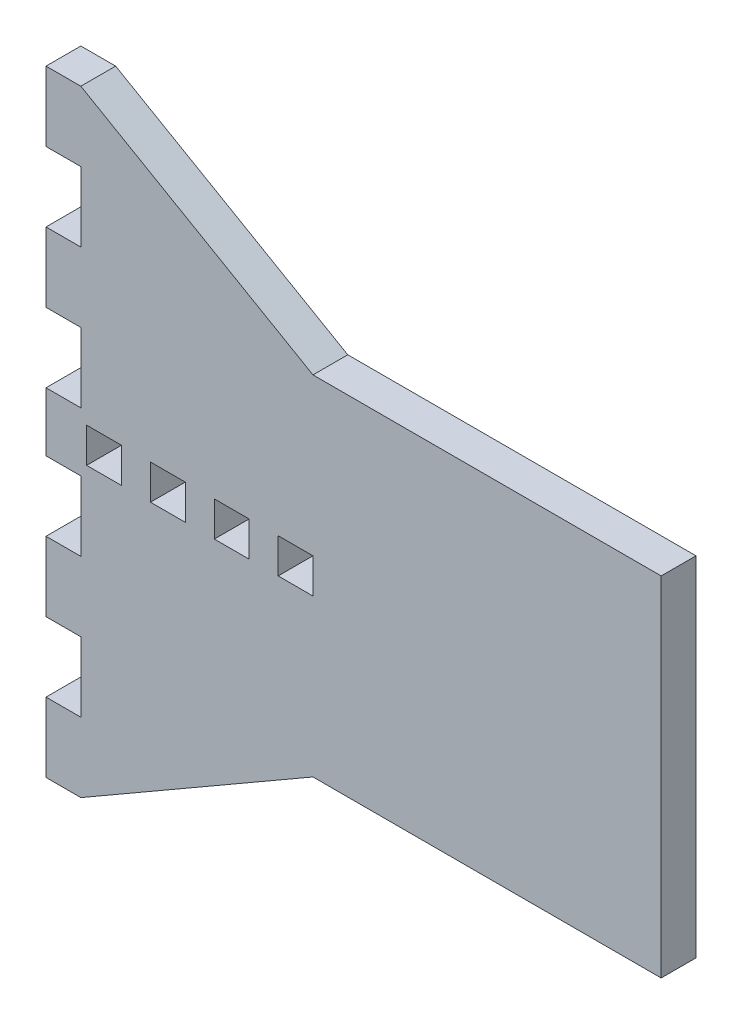
SolidWorks part; units mm, degrees
ref_plane "Front Plane" through (0, 0, 0) normal (0, 0, 1) x (1, 0, 0)
ref_plane "Top Plane" through (0, 0, 0) normal (0, 1, 0) x (1, 0, 0)
ref_plane "Right Plane" through (0, 0, 0) normal (1, 0, 0) x (0, 0, -1)
sketch "Sketch1" plane through (0, 0, 0) normal (0, 0, 1) x (1, 0, 0)
  line L0 (-66.7906, 0) -> (77.661, 0) construction
  line L1 (0, 53.9016) -> (0, -59.5601) construction
  line L9 (-35, 26.54) -> (-35, -26.54)
  line L10 (-15, 15) -> (15, 15)
  line L12 (-15, -15) -> (15, -15)
  line L13 (15, 15) -> (15, -15)
  line L14 (-15, 15) -> (15, -15) construction
  line L15 (-15, -15) -> (15, 15) construction
  line L16 (-35, 26.54) -> (-15, 15)
  line L17 (-15, -15) -> (-35, -26.54)
  circle A1 centre (0, 0) radius 11
  dimension "D1" = 22
  dimension "D2" = 30
  dimension "D3" = 30
  dimension "D4" = 35
  dimension "D5" = 26.54
  dimension "D6" = 26.54
  dimension "D7" = 15
extrude "Boss-Extrude1" add sketch "Sketch1" along normal blind 3 contours A1 | L17 L12 L13 L10 L16 L9 A1 region at (-15.9472, 0, 0) region at (0, 0, 0)
extrude "Cut-Extrude1" cut sketch "Sketch1<3>" along normal blind 1 contours A1
sketch "Sketch1<3>" plane through (0, 0, 0) normal (0, 0, 1) x (1, 0, 0) same geometry as "Sketch1"
sketch "Sketch2" plane through (0, 0, 0) normal (0, 0, -1) x (-1, 0, 0)
  line L0 (70.454, 0) -> (-33.1814, 0) construction
  line L1 (35, -26.54) -> (38, -26.54)
  line L2 (35, 47.2621) -> (35, -36.057) construction
  line L3 (38, -26.54) -> (38, -20.54)
  line L4 (38, -20.54) -> (35, -20.54)
  line L5 (35, -14.54) -> (38, -14.54)
  line L6 (38, -14.54) -> (38, -8.54)
  line L7 (38, -8.54) -> (35, -8.54)
  line L8 (35, -2.54) -> (38, -2.54)
  line L9 (38, -2.54) -> (38, 2.54)
  line L10 (38, 2.54) -> (35, 2.54)
  line L11 (38, 8.54) -> (35, 8.54)
  line L12 (38, 14.54) -> (38, 8.54)
  line L13 (35, 14.54) -> (38, 14.54)
  line L14 (38, 20.54) -> (35, 20.54)
  line L15 (35, 26.54) -> (38, 26.54)
  line L16 (38, 26.54) -> (38, 20.54)
  line L17 (35, -26.54) -> (35, -20.54)
  line L18 (35, -14.54) -> (35, -8.54)
  line L19 (35, -2.54) -> (35, 2.54)
  line L20 (35, 26.54) -> (35, 20.54)
  line L21 (35, 14.54) -> (35, 8.54)
  dimension "D1" = 6
  dimension "D2" = 3
  dimension "D3" = 3
  dimension "D4" = 6
  dimension "D5" = 6
  dimension "D6" = 6
  dimension "D7" = 5.08
  dimension "D8" = 3
extrude "Boss-Extrude2" add sketch "Sketch2" against normal blind 3 separate body
sketch "Sketch3" plane through (0, 0, 0) normal (0, 0, -1) x (-1, 0, 0)
  line L0 (15, 25.294) -> (15, -24.0176) construction
  line L1 (-21.0908, 0) -> (51.3663, 0) construction
  line L2 (20.5, 1.5) -> (23.5, 1.5)
  line L3 (15, 1.5) -> (18, 1.5)
  line L4 (15, 1.5) -> (15, -1.5)
  line L5 (15, -1.5) -> (18, -1.5)
  line L6 (18, 1.5) -> (18, -1.5)
  line L7 (20.5, 1.5) -> (20.5, -1.5)
  line L8 (20.5, -1.5) -> (23.5, -1.5)
  line L9 (23.5, 1.5) -> (23.5, -1.5)
  line L10 (26, 1.5) -> (29, 1.5)
  line L11 (26, 1.5) -> (26, -1.5)
  line L12 (26, -1.5) -> (29, -1.5)
  line L13 (29, 1.5) -> (29, -1.5)
  line L14 (31.5, 1.5) -> (34.5, 1.5)
  line L15 (31.5, 1.5) -> (31.5, -1.5)
  line L16 (31.5, -1.5) -> (34.5, -1.5)
  line L17 (34.5, 1.5) -> (34.5, -1.5)
  dimension "D1" = 3
  dimension "D2" = 3
  dimension "D3" = 1.5
  dimension "D4" = 4
  dimension "D5" = 2.5
extrude "Cut-Extrude2" cut sketch "Sketch3" against normal blind 3
combine bodies "Combine1" operation type add bodies to combine 105 103 106 108 107 104
